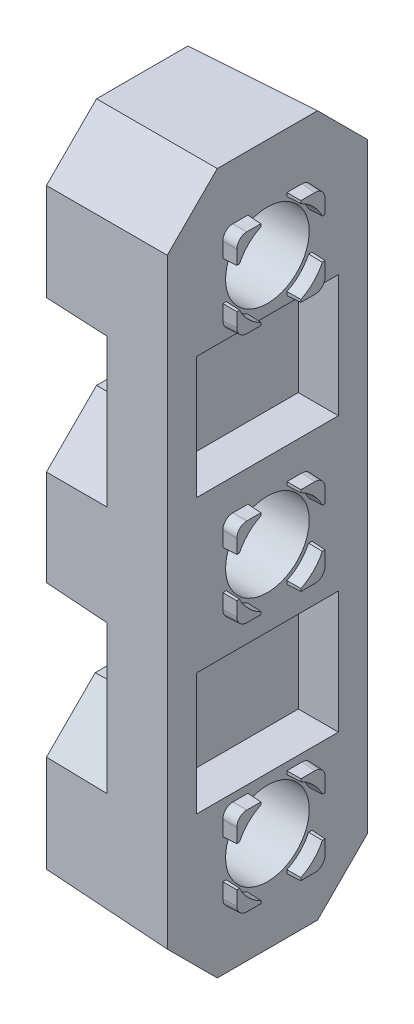
SolidWorks part; units mm, degrees
ref_plane "Front Plane" through (0, 0, 0) normal (0, 0, 1) x (1, 0, 0)
ref_plane "Top Plane" through (0, 0, 0) normal (0, 1, 0) x (1, 0, 0)
ref_plane "Right Plane" through (0, 0, 0) normal (1, 0, 0) x (0, 0, -1)
ref_plane "Plane1" through (88.9762, 0, 0) normal (1, 0, 0) x (0, 0, -1)
sketch "Sketch1" plane through (88.9762, 0, 0) normal (1, 0, 0) x (0, 0, -1)
  line L0 (7.8417, 8.8578) -> (17.5583, 8.8578)
  line L1 (17.5583, 8.8578) -> (17.5583, 43.9743)
  line L2 (17.5583, 43.9743) -> (7.8417, 43.9743)
  line L3 (7.8417, 43.9743) -> (7.8417, 8.8578)
extrude "Boss-Extrude1" add sketch "Sketch1" against normal blind 6.35
sketch "Sketch2" plane through (82.6262, 0, 0) normal (-1, 0, 0) x (0, 0, 1)
  line L0 (-7.8417, 36.5093) -> (-10.3153, 34.0358)
  line L1 (-10.3153, 34.0358) -> (-11.7, 34.0358)
  line L2 (-11.7, 34.0358) -> (-11.7, 31.3853)
  line L3 (-11.7, 31.3853) -> (-10.3802, 31.3853)
  line L4 (-10.3802, 31.3853) -> (-7.8417, 28.8468)
  line L5 (-7.8417, 28.8468) -> (-7.8417, 36.5093)
extrude "Cut-Extrude1" cut sketch "Sketch2" against normal blind 3.175
sketch "Sketch3" plane through (82.6262, 0, 0) normal (-1, 0, 0) x (0, 0, 1)
  line L0 (-7.8417, 23.9852) -> (-10.3802, 21.4468)
  line L1 (-10.3802, 21.4468) -> (-11.7, 21.4468)
  line L2 (-11.7, 21.4468) -> (-11.7, 18.7963)
  line L3 (-11.7, 18.7963) -> (-10.3153, 18.7963)
  line L4 (-10.3153, 18.7963) -> (-7.8417, 16.3228)
  line L5 (-7.8417, 16.3228) -> (-7.8417, 23.9852)
extrude "Cut-Extrude2" cut sketch "Sketch3" against normal blind 3.175
sketch "Sketch4" plane through (82.6262, 0, 0) normal (-1, 0, 0) x (0, 0, 1)
  line L0 (-17.5583, 16.3228) -> (-15.0847, 18.7963)
  line L1 (-15.0847, 18.7963) -> (-13.7, 18.7963)
  line L2 (-13.7, 18.7963) -> (-13.7, 21.4468)
  line L3 (-13.7, 21.4468) -> (-15.0198, 21.4468)
  line L4 (-15.0198, 21.4468) -> (-17.5583, 23.9852)
  line L5 (-17.5583, 23.9852) -> (-17.5583, 16.3228)
extrude "Cut-Extrude3" cut sketch "Sketch4" against normal blind 3.175
sketch "Sketch5" plane through (82.6262, 0, 0) normal (-1, 0, 0) x (0, 0, 1)
  line L0 (-17.5583, 28.8468) -> (-15.0198, 31.3853)
  line L1 (-15.0198, 31.3853) -> (-13.7, 31.3853)
  line L2 (-13.7, 31.3853) -> (-13.7, 34.0358)
  line L3 (-13.7, 34.0358) -> (-15.0847, 34.0358)
  line L4 (-15.0847, 34.0358) -> (-17.5583, 36.5093)
  line L5 (-17.5583, 36.5093) -> (-17.5583, 28.8468)
extrude "Cut-Extrude4" cut sketch "Sketch5" against normal blind 3.175
sketch "Sketch6" plane through (88.9762, 0, 0) normal (1, 0, 0) x (0, 0, -1)
  line L0 (11.7094, 24.3276) -> (11.7094, 24.1554)
  line L1 (11.7094, 24.1554) -> (10.4394, 24.1554)
  line L2 (10.4394, 24.1554) -> (10.4394, 25.4254)
  line L3 (10.4394, 25.4254) -> (10.6116, 25.4254)
  arc A0 (10.6116, 25.4254) -> (11.7094, 24.3276) centre (12.7, 26.416) ccw
extrude "Boss-Extrude2" add sketch "Sketch6" along normal blind 0.6858 draft 2
sketch "Sketch7" plane through (88.9762, 0, 0) normal (1, 0, 0) x (0, 0, -1)
  line L0 (14.7884, 25.4254) -> (14.9606, 25.4254)
  line L1 (14.9606, 25.4254) -> (14.9606, 24.1554)
  line L2 (14.9606, 24.1554) -> (13.6906, 24.1554)
  line L3 (13.6906, 24.1554) -> (13.6906, 24.3276)
  arc A0 (13.6906, 24.3276) -> (14.7884, 25.4254) centre (12.7, 26.416) ccw
extrude "Boss-Extrude3" add sketch "Sketch7" along normal blind 0.6858 draft 2
sketch "Sketch8" plane through (88.9762, 0, 0) normal (1, 0, 0) x (0, 0, -1)
  line L0 (13.6906, 28.5044) -> (13.6906, 28.6766)
  line L1 (13.6906, 28.6766) -> (14.9606, 28.6766)
  line L2 (14.9606, 28.6766) -> (14.9606, 27.4066)
  line L3 (14.9606, 27.4066) -> (14.7884, 27.4066)
  arc A0 (14.7884, 27.4066) -> (13.6906, 28.5044) centre (12.7, 26.416) ccw
extrude "Boss-Extrude4" add sketch "Sketch8" along normal blind 0.6858 draft 2
sketch "Sketch9" plane through (88.9762, 0, 0) normal (1, 0, 0) x (0, 0, -1)
  line L0 (10.6116, 27.4066) -> (10.4394, 27.4066)
  line L1 (10.4394, 27.4066) -> (10.4394, 28.6766)
  line L2 (10.4394, 28.6766) -> (11.7094, 28.6766)
  line L3 (11.7094, 28.6766) -> (11.7094, 28.5044)
  arc A0 (11.7094, 28.5044) -> (10.6116, 27.4066) centre (12.7, 26.416) ccw
extrude "Boss-Extrude5" add sketch "Sketch9" along normal blind 0.6858 draft 2
sketch "Sketch10" plane through (88.9762, 0, 0) normal (1, 0, 0) x (0, 0, -1)
  line L0 (11.7094, 37.0276) -> (11.7094, 36.8554)
  line L1 (11.7094, 36.8554) -> (10.4394, 36.8554)
  line L2 (10.4394, 36.8554) -> (10.4394, 38.1254)
  line L3 (10.4394, 38.1254) -> (10.6116, 38.1254)
  arc A0 (10.6116, 38.1254) -> (11.7094, 37.0276) centre (12.7, 39.116) ccw
extrude "Boss-Extrude6" add sketch "Sketch10" along normal blind 0.6858 draft 2
sketch "Sketch11" plane through (88.9762, 0, 0) normal (1, 0, 0) x (0, 0, -1)
  line L0 (14.7884, 38.1254) -> (14.9606, 38.1254)
  line L1 (14.9606, 38.1254) -> (14.9606, 36.8554)
  line L2 (14.9606, 36.8554) -> (13.6906, 36.8554)
  line L3 (13.6906, 36.8554) -> (13.6906, 37.0276)
  arc A0 (13.6906, 37.0276) -> (14.7884, 38.1254) centre (12.7, 39.116) ccw
extrude "Boss-Extrude7" add sketch "Sketch11" along normal blind 0.6858 draft 2
sketch "Sketch12" plane through (88.9762, 0, 0) normal (1, 0, 0) x (0, 0, -1)
  line L0 (13.6906, 41.2044) -> (13.6906, 41.3766)
  line L1 (13.6906, 41.3766) -> (14.9606, 41.3766)
  line L2 (14.9606, 41.3766) -> (14.9606, 40.1066)
  line L3 (14.9606, 40.1066) -> (14.7884, 40.1066)
  arc A0 (14.7884, 40.1066) -> (13.6906, 41.2044) centre (12.7, 39.116) ccw
extrude "Boss-Extrude8" add sketch "Sketch12" along normal blind 0.6858 draft 2
sketch "Sketch13" plane through (88.9762, 0, 0) normal (1, 0, 0) x (0, 0, -1)
  line L0 (10.6116, 40.1066) -> (10.4394, 40.1066)
  line L1 (10.4394, 40.1066) -> (10.4394, 41.3766)
  line L2 (10.4394, 41.3766) -> (11.7094, 41.3766)
  line L3 (11.7094, 41.3766) -> (11.7094, 41.2044)
  arc A0 (11.7094, 41.2044) -> (10.6116, 40.1066) centre (12.7, 39.116) ccw
extrude "Boss-Extrude9" add sketch "Sketch13" along normal blind 0.6858 draft 2
sketch "Sketch14" plane through (88.9762, 0, 0) normal (1, 0, 0) x (0, 0, -1)
  line L0 (11.7094, 11.6276) -> (11.7094, 11.4554)
  line L1 (11.7094, 11.4554) -> (10.4394, 11.4554)
  line L2 (10.4394, 11.4554) -> (10.4394, 12.7254)
  line L3 (10.4394, 12.7254) -> (10.6116, 12.7254)
  arc A0 (10.6116, 12.7254) -> (11.7094, 11.6276) centre (12.7, 13.716) ccw
extrude "Boss-Extrude10" add sketch "Sketch14" along normal blind 0.6858 draft 2
sketch "Sketch15" plane through (88.9762, 0, 0) normal (1, 0, 0) x (0, 0, -1)
  line L0 (14.7884, 12.7254) -> (14.9606, 12.7254)
  line L1 (14.9606, 12.7254) -> (14.9606, 11.4554)
  line L2 (14.9606, 11.4554) -> (13.6906, 11.4554)
  line L3 (13.6906, 11.4554) -> (13.6906, 11.6276)
  arc A0 (13.6906, 11.6276) -> (14.7884, 12.7254) centre (12.7, 13.716) ccw
extrude "Boss-Extrude11" add sketch "Sketch15" along normal blind 0.6858 draft 2
sketch "Sketch16" plane through (88.9762, 0, 0) normal (1, 0, 0) x (0, 0, -1)
  line L0 (13.6906, 15.8044) -> (13.6906, 15.9766)
  line L1 (13.6906, 15.9766) -> (14.9606, 15.9766)
  line L2 (14.9606, 15.9766) -> (14.9606, 14.7066)
  line L3 (14.9606, 14.7066) -> (14.7884, 14.7066)
  arc A0 (14.7884, 14.7066) -> (13.6906, 15.8044) centre (12.7, 13.716) ccw
extrude "Boss-Extrude12" add sketch "Sketch16" along normal blind 0.6858 draft 2
sketch "Sketch17" plane through (88.9762, 0, 0) normal (1, 0, 0) x (0, 0, -1)
  line L0 (10.6116, 14.7066) -> (10.4394, 14.7066)
  line L1 (10.4394, 14.7066) -> (10.4394, 15.9766)
  line L2 (10.4394, 15.9766) -> (11.7094, 15.9766)
  line L3 (11.7094, 15.9766) -> (11.7094, 15.8044)
  arc A0 (11.7094, 15.8044) -> (10.6116, 14.7066) centre (12.7, 13.716) ccw
extrude "Boss-Extrude13" add sketch "Sketch17" along normal blind 0.6858 draft 2
sketch "Sketch18" plane through (88.9762, 0, 0) normal (1, 0, 0) x (0, 0, -1)
  line L0 (9.1, 16.366) -> (16.3, 16.366)
  line L1 (16.3, 16.366) -> (16.3, 22.566)
  line L2 (16.3, 22.566) -> (9.1, 22.566)
  line L3 (9.1, 22.566) -> (9.1, 16.366)
extrude "Cut-Extrude5" cut sketch "Sketch18" against normal blind 2.032
sketch "Sketch19" plane through (88.9762, 0, 0) normal (1, 0, 0) x (0, 0, -1)
  line L0 (9.1, 36.466) -> (9.1, 30.266)
  line L1 (9.1, 30.266) -> (16.3, 30.266)
  line L2 (16.3, 30.266) -> (16.3, 36.466)
  line L3 (16.3, 36.466) -> (9.1, 36.466)
extrude "Cut-Extrude6" cut sketch "Sketch19" against normal blind 2.032
draft "Draft1" type of draft neutral plane draft angle 2.827 faces to draft 4 face at (84.2137, 30.116, -9.111) face at (84.2137, 22.716, -9.111) face at (84.2137, 22.716, -16.289) face at (84.2137, 30.116, -16.289) neutral plane through (82.6262, 0, 0) neutral plane normal (-1, 0, 0) parameters "D1"=2.827
draft "Draft2" type of draft neutral plane draft angle 2 faces to draft 16 face at (85.8012, 43.9743, -12.7) face at (84.2137, 35.2725, -9.0785) face at (84.2137, 34.0358, -11.0076) face at (84.2137, 31.3853, -10.9847) face at (84.2137, 21.4468, -10.9847) face at (84.2137, 18.7963, -11.0076) face at (84.2137, 17.5595, -9.0785) face at (84.7429, 26.416, -7.8417) face at (85.8012, 8.8578, -12.7) face at (84.2137, 17.5595, -16.3215) face at (84.2137, 18.7963, -14.3924) face at (84.2137, 21.4468, -14.4153) face at (84.2137, 31.3853, -14.4153) face at (84.2137, 34.0358, -14.3924) face at (84.2137, 35.2725, -16.3215) face at (84.7429, 26.416, -17.5583) neutral plane through (82.6262, 0, 0) neutral plane normal (-1, 0, 0) parameters "D1"=2
hole_wizard "Hole1" positions "Sketch21" profile "Sketch20" legacy
sketch "Sketch21" plane through (82.6262, 0, 0) normal (-1, 0, 0) x (0, 0, 1)
  point P0 (-12.7, 26.416)
  point P1 (-12.7, 13.716)
  point P2 (-12.7, 39.116)
sketch "Sketch20" plane through (82.6262, 26.416, -12.7) normal (0, 1, 0) x (0, 0, 1)
  line L0 (0, 0) -> (0, 7.0358)
  line L1 (0, 7.0358) -> (2.1209, 7.0358)
  line L2 (2.1209, 7.0358) -> (2.1209, 0)
  line L3 (2.1209, 0) -> (0, 0)
  line L4 (0, 110) -> (0, -10) construction
  dimension "Diameter" = 4.2418
  dimension "Depth" = 7.0358
chamfer "Chamfer1" distance 2.5369 angle 44.965 4 edges at (85.8012, 8.7469, -17.6691) (85.8012, 44.0851, -17.6691) (85.8012, 8.7469, -7.7309) (85.8012, 44.0851, -7.7309) first distance on face at (85.8012, 8.7469, -12.7) first distance on face at (85.8012, 44.0851, -12.7)
fillet "Fillet1" radius 0.508 12 edges at (89.3191, 41.3646, -10.4514) (89.3191, 15.9646, -10.4514) (89.3191, 11.4674, -14.9486) (89.3191, 24.1674, -10.4514) (89.3191, 41.3646, -14.9486) (89.3191, 24.1674, -14.9486) (89.3191, 11.4674, -10.4514) (89.3191, 28.6646, -14.9486) (89.3191, 15.9646, -14.9486) (89.3191, 36.8674, -10.4514) (89.3191, 36.8674, -14.9486) (89.3191, 28.6646, -10.4514) tangent propagation no
